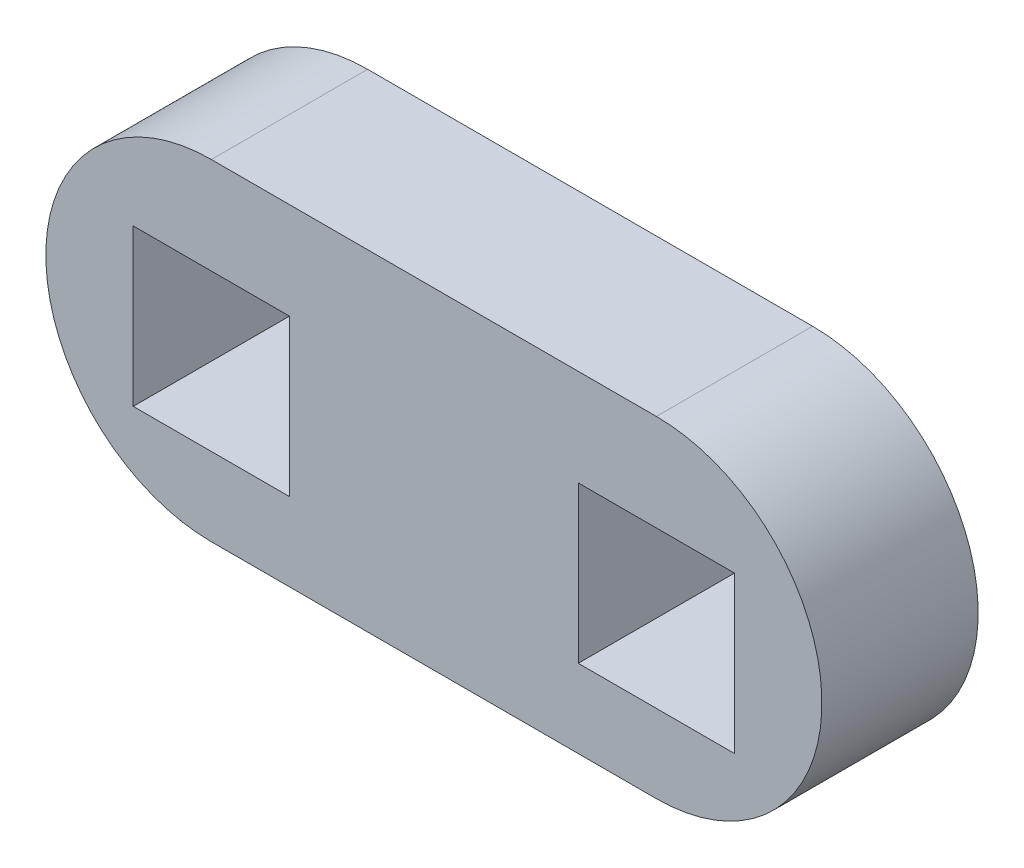
SolidWorks part; units mm, degrees
ref_plane "Front Plane" through (0, 0, 0) normal (0, 0, 1) x (1, 0, 0)
ref_plane "Top Plane" through (0, 0, 0) normal (0, 1, 0) x (1, 0, 0)
ref_plane "Right Plane" through (0, 0, 0) normal (1, 0, 0) x (0, 0, -1)
sketch "Sketch1" plane through (0, 0, 0) normal (0, 0, 1) x (1, 0, 0)
  line L0 (384.6105, 118.344) -> (367.5378, 118.344) construction
  line L1 (387.6077, 114.994) -> (381.6133, 114.994)
  line L2 (387.6077, 114.994) -> (387.6077, 120.9884)
  line L3 (387.6077, 120.9884) -> (381.6133, 120.9884)
  line L4 (381.6133, 114.994) -> (381.6133, 120.9884)
  line L5 (364.5406, 120.9884) -> (370.535, 120.9884)
  line L6 (364.5406, 120.9884) -> (364.5406, 114.994)
  line L7 (364.5406, 114.994) -> (370.535, 114.994)
  line L8 (370.535, 120.9884) -> (370.535, 114.994)
  line L9 (384.6105, 111.994) -> (367.5378, 111.994)
  line L10 (384.6105, 124.694) -> (367.5378, 124.694)
  arc A0 (384.6105, 111.994) -> (384.6105, 124.694) centre (384.6105, 118.344) ccw
  arc A1 (367.5378, 124.694) -> (367.5378, 111.994) centre (367.5378, 118.344) ccw
  point P10 (376.0742, 118.344)
extrude "Boss-Extrude1" add sketch "Sketch1" along normal blind 5.9944
